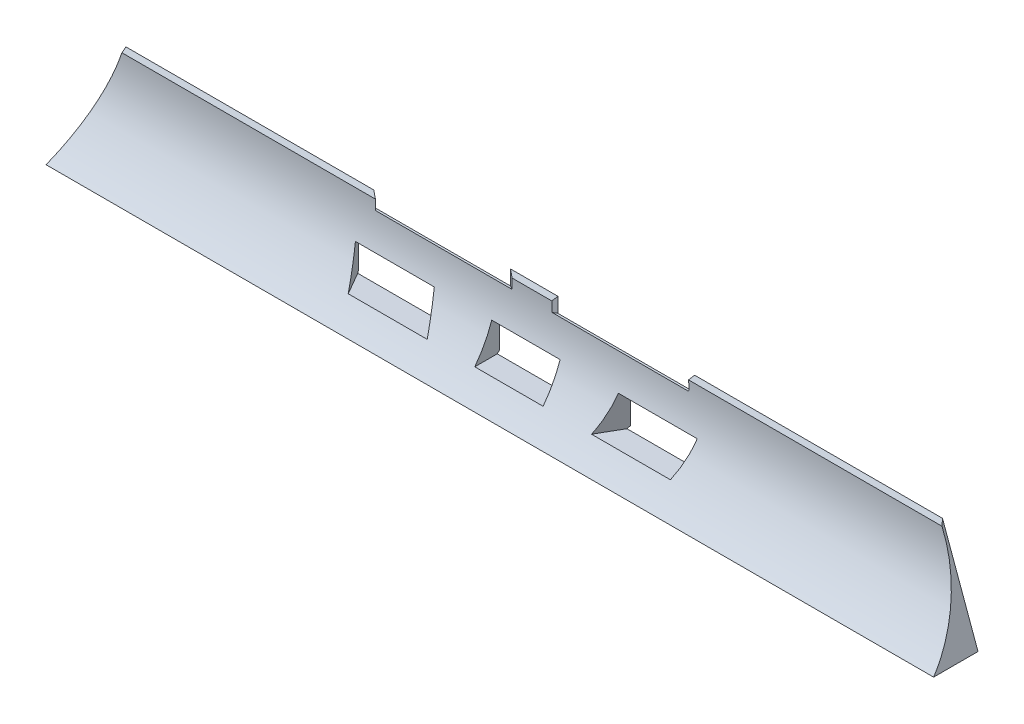
SolidWorks part; units mm, degrees
material "ABS"
ref_plane "Front Plane" through (0, 0, 0) normal (0, 0, 1) x (1, 0, 0)
ref_plane "Top Plane" through (0, 0, 0) normal (0, 1, 0) x (1, 0, 0)
ref_plane "Right Plane" through (0, 0, 0) normal (1, 0, 0) x (0, 0, -1)
sketch "Sketch1" plane through (0, 0, 0) normal (1, 0, 0) x (0, 0, -1)
  line L0 (0, 0) -> (-10, 0)
  line L1 (-10, 0) -> (0, 22)
  line L2 (0, 22) -> (0, 0)
  dimension "D1" = 10
  dimension "D2" = 22
extrude "Boss-Extrude1" add sketch "Sketch1" along normal blind 200
sketch "Sketch2" plane through (200, 0, 0) normal (1, 0, 0) x (0, 0, -1)
  line L0 (0, 22) -> (-10, 0) construction
  line L1 (-10, 0) -> (0, 0) construction
  line L2 (0, 0) -> (0, 22) construction
  line L3 (-10, 0) -> (-0.5, 20.9)
  arc A0 (-10, 0) -> (-0.5, 20.9) centre (-25.4682, 19.6401) ccw
  dimension "D3" = 25
  dimension "D1" = 0
  dimension "D2" = 0.5
extrude "Cut-Extrude1" cut sketch "Sketch2" against normal through all
sketch "Sketch4" plane through (200, 0, 0) normal (1, 0, 0) x (0, 0, -1)
  line L0 (-5, 0) -> (0, 5)
  line L1 (-10, 0) -> (0, 0) construction
  line L2 (0, 0) -> (0, 22) construction
  line L3 (0, 5) -> (0, 0)
  line L4 (0, 0) -> (-5, 0)
  dimension "D1" = 5
  dimension "D2" = 5
extrude "Cut-Extrude2" cut sketch "Sketch4" against normal through all
sketch "Sketch5" plane through (0, 0, 0) normal (0, 0, -1) x (-1, 0, 0)
  line L0 (0, 0) -> (-200, 0) construction
  line L1 (-200, 5) -> (-197, 5)
  line L2 (-200, 5) -> (-200, 0)
  line L3 (-200, 0) -> (-197, 0)
  line L4 (-197, 5) -> (-197, 0)
  dimension "D1" = 3
extrude "Boss-Extrude2" add sketch "Sketch5" against normal up to surface up to face at (100, 2.5, 2.5)
ref_plane "Plane1" through (100, 0, 0) normal (1, 0, 0) x (0, 0, -1)
sketch "Sketch6" plane through (0, 0, 0) normal (0, 0, -1) x (-1, 0, 0)
  line L0 (-200, 22) -> (-191.9927, 22)
  line L1 (-200, 22) -> (0, 22) construction
  line L2 (-191.9927, 22) -> (-200, 0)
  line L3 (-200, 22) -> (-200, 0)
  dimension "D1" = 20
extrude "Cut-Extrude3" cut sketch "Sketch6" against normal through all
mirror "Mirror2" about plane through (100, 0, 0) normal (1, 0, 0) of "Cut-Extrude3", "Boss-Extrude2"
sketch "Sketch7" plane through (0, 0, 0) normal (0, 0, -1) x (-1, 0, 0)
  line L1 (-159.8316, 13.465) -> (-167.8316, 13.465)
  line L2 (-159.8316, 13.465) -> (-159.8316, 0.465)
  line L3 (-159.8316, 0.465) -> (-167.8316, 0.465)
  line L4 (-167.8316, 13.465) -> (-167.8316, 0.465)
  line L5 (-160.8316, 13.465) -> (-166.8316, 13.465) construction
  line L7 (-166.8316, 13.465) -> (-166.8316, 2.465) construction
  dimension "D1" = 8
  dimension "D2" = 1
  dimension "D3" = 13
extrude "Boss-Extrude3" add sketch "Sketch7" against normal up to next
sketch "Sketch8" plane through (0, 0, 0) normal (0, 0, -1) x (-1, 0, 0)
  line L1 (-165.5637, 8.5) -> (-167.2957, 5.5)
  line L2 (-167.2957, 5.5) -> (-165.5637, 2.5)
  line L3 (-165.5637, 2.5) -> (-162.0995, 2.5)
  line L4 (-162.0995, 2.5) -> (-160.3675, 5.5)
  line L5 (-160.3675, 5.5) -> (-162.0995, 8.5)
  line L6 (-162.0995, 8.5) -> (-165.5637, 8.5)
  line L7 (-167.8316, 0) -> (-159.8316, 0) construction
  line L8 (-165.3316, 10.465) -> (-165.3316, 5.465) construction
  circle A2 centre (-163.8316, 5.5) radius 3 construction
  point P13 (-163.8316, 8.5)
  dimension "D1" = 6
  dimension "D2" = 1.5
  dimension "D3" = 5.5
extrude "Cut-Extrude4" cut sketch "Sketch8" against normal blind 1.8 contours L5 L6 L1 L2 L3 L4 | L1 L2 L3 L4 L5 L6 region at (163.8316, 5.5, 0)
mirror "Mirror3" about plane through (100, 0, 0) normal (1, 0, 0) of "Cut-Extrude4", "Boss-Extrude3"
sketch "Sketch9" plane through (0, 0, 0) normal (0, 0, 1) x (1, 0, 0)
  line L1 (92.2158, 4.465) -> (107.6158, 4.465)
  line L2 (92.2158, 4.465) -> (92.2158, 11.665)
  line L3 (92.2158, 11.665) -> (107.6158, 11.665)
  line L4 (107.6158, 4.465) -> (107.6158, 11.665)
extrude "Cut-Extrude6" cut sketch "Sketch9" along normal through all
ref_plane "Plane2" through (32.136, 0, -55.6612) normal (-0.5, 0, 0.866) x (0.866, 0, 0.5)
sketch "Sketch10" plane through (32.136, 0, -55.6612) normal (-0.5, 0, 0.866) x (0.866, 0, 0.5)
  line L1 (105.439, 4.465) -> (120.839, 4.465)
  line L2 (105.439, 4.465) -> (105.439, 11.665)
  line L3 (105.439, 11.665) -> (120.839, 11.665)
  line L4 (120.839, 4.465) -> (120.839, 11.665)
extrude "Cut-Extrude8" cut sketch "Sketch10" along normal blind 15.8 and the other way blind 6.8
ref_plane "Plane3" through (115.6697, 0, -66.7819) normal (-0.866, 0, 0.5) x (0.5, 0, 0.866)
sketch "Sketch11" plane through (115.6697, 0, -66.7819) normal (-0.866, 0, 0.5) x (0.5, 0, 0.866)
  line L1 (68.0717, 27.465) -> (52.6717, 27.465)
  line L2 (68.0717, 27.465) -> (68.0717, 18.665)
  line L3 (68.0717, 18.665) -> (52.6717, 18.665)
  line L4 (52.6717, 27.465) -> (52.6717, 18.665)
  line L7 (52.6717, 27.465) -> (52.6717, 20.265) construction
  line L8 (47.1217, 18.665) -> (73.6217, 18.665) construction
extrude "Cut-Extrude9" cut sketch "Sketch11" along normal blind 97.8
mirror "Mirror4" about plane through (100, 0, 0) normal (1, 0, 0) of "Cut-Extrude8", "Cut-Extrude9"
